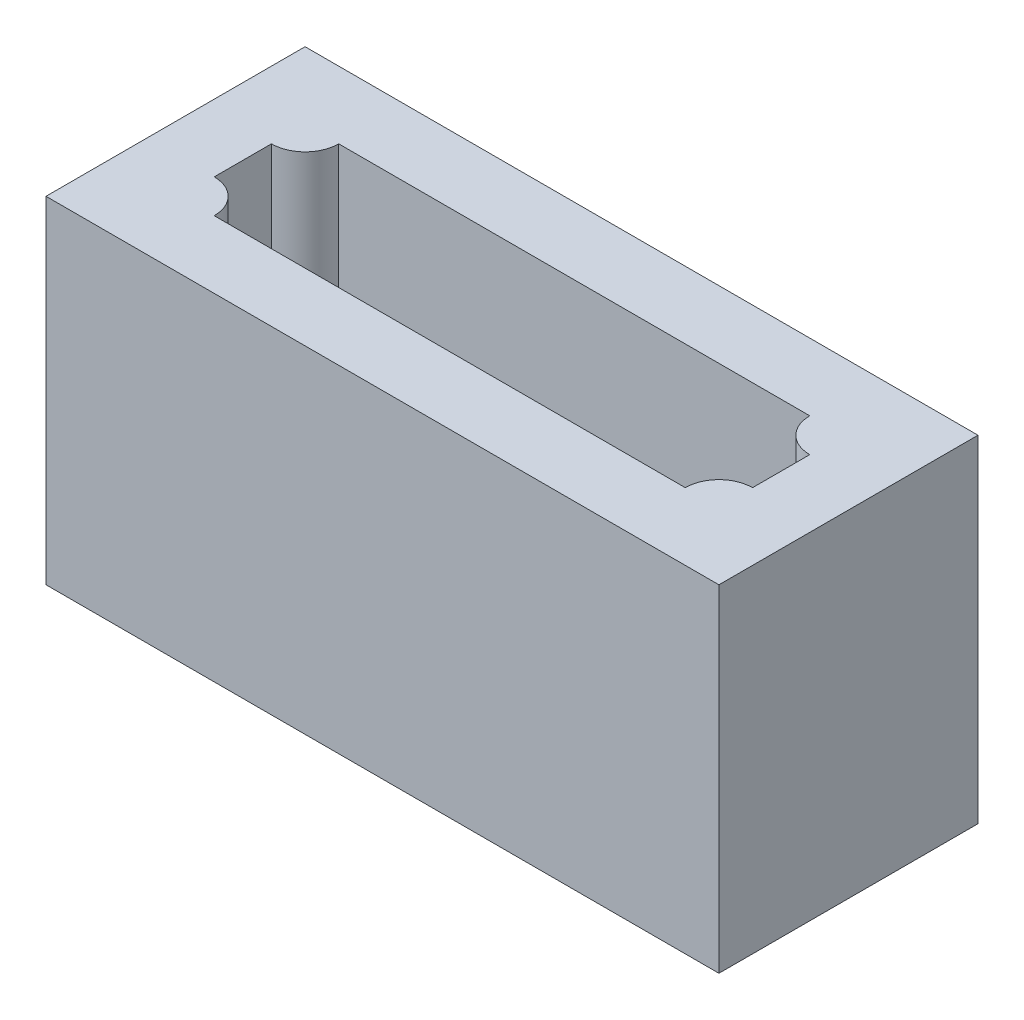
SolidWorks part; units mm, degrees
ref_plane "Front Plane" through (0, 0, 0) normal (0, 0, 1) x (1, 0, 0)
ref_plane "Top Plane" through (0, 0, 0) normal (0, 1, 0) x (1, 0, 0)
ref_plane "Right Plane" through (0, 0, 0) normal (1, 0, 0) x (0, 0, -1)
sketch "Sketch1" plane through (0, 0, 0) normal (0, 1, 0) x (1, 0, 0)
  line L0 (-50, 19.25) -> (50, 19.25)
  line L1 (-40, 9.25) -> (40, 9.25)
  line L2 (-40, 9.25) -> (-40, -9.25)
  line L3 (-40, -9.25) -> (40, -9.25)
  line L4 (40, 9.25) -> (40, -9.25)
  line L5 (-40, 9.25) -> (40, -9.25) construction
  line L6 (-40, -9.25) -> (40, 9.25) construction
  line L7 (50, 19.25) -> (50, -19.25)
  line L8 (-50, -19.25) -> (50, -19.25)
  line L9 (-50, 19.25) -> (-50, -19.25)
  point P0 (0, 0)
  dimension "D1" = 80
  dimension "D2" = 18.5
  dimension "D3" = 10
extrude "Boss-Extrude1" add sketch "Sketch1" along normal blind 25 and the other way blind 25
sketch "Sketch2" plane through (0, 0, 0) normal (0, 1, 0) x (1, 0, 0)
  circle A0 centre (40, 9.25) radius 5
  circle A1 centre (40, -9.25) radius 5
  circle A2 centre (-40, 9.25) radius 5
  circle A3 centre (-40, -9.25) radius 5
  dimension "D1" = 10
extrude "Boss-Extrude2" add sketch "Sketch2" along normal through all and the other way through all
